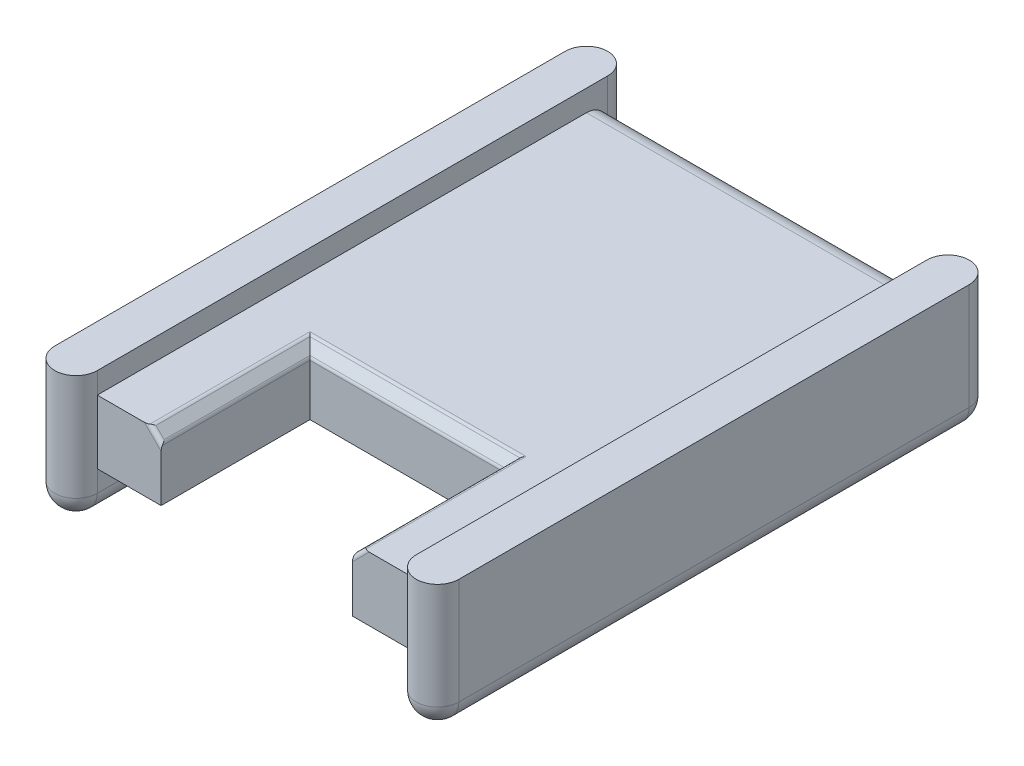
SolidWorks part; units mm, degrees
ref_plane "Front Plane" through (0, 0, 0) normal (0, 0, 1) x (1, 0, 0)
ref_plane "Top Plane" through (0, 0, 0) normal (0, 1, 0) x (1, 0, 0)
ref_plane "Right Plane" through (0, 0, 0) normal (1, 0, 0) x (0, 0, -1)
sketch "Sketch1" plane through (0, 0, 0) normal (0, 0, 1) x (1, 0, 0)
  line L1 (0, 0) -> (750, 0)
  line L2 (0, 0) -> (0, 150)
  line L3 (0, 150) -> (750, 150)
  line L4 (750, 0) -> (750, 150)
  dimension "D1" = 150
  dimension "D2" = 750
extrude "Boss-Extrude1" add sketch "Sketch1" against normal blind 1200
sketch "Sketch2" plane through (0, 150, 0) normal (0, 1, 0) x (1, 0, 0)
  line L0 (375, 1200) -> (375, 0) construction
  line L2 (0, 1200) -> (0, 0)
  line L4 (-100, 1200) -> (-100, 0)
  line L5 (750, 1200) -> (0, 1200) construction
  line L6 (750, 0) -> (0, 0) construction
  line L8 (850, 1200) -> (850, 0)
  line L10 (750, 1200) -> (750, 0)
  arc A4 (0, 1200) -> (-100, 1200) centre (-50, 1200) ccw
  arc A5 (850, 1200) -> (750, 1200) centre (800, 1200) ccw
  arc A6 (750, 0) -> (850, 0) centre (800, 0) ccw
  arc A7 (-100, 0) -> (0, 0) centre (-50, 0) ccw
  dimension "D1" = 100
extrude "Boss-Extrude8" add sketch "Sketch2" against normal blind 250 and the other way blind 50
fillet "Fillet2" radius 50 8 edges at (850, -100, -600) (800, -100, -1250) (750, -100, -600) (800, -100, 50) (-100, -100, -600) (-50, -100, 50) (0, -100, -600) (-50, -100, -1250)
fillet "Fillet3" radius 50 2 edges at (375, 150, -1200) (375, 0, -1200)
sketch "Sketch6" plane through (0, 150, 0) normal (0, 1, 0) x (1, 0, 0)
  line L0 (750, 0) -> (0, 0) construction
  line L5 (150, 0) -> (150, 350)
  line L6 (375, 0) -> (375, 423.0484) construction
  line L7 (600, 0) -> (150, 0)
  line L8 (600, 0) -> (600, 350)
  line L9 (600, 350) -> (150, 350)
  point P0 (375, 0)
  dimension "D3" = 350
extrude "Cut-Extrude1" cut sketch "Sketch6" against normal blind 250
chamfer "Chamfer1" distance 25 angle 45 1 edges at (375, 150, -350)
chamfer "Chamfer2" distance 25 angle 45 2 edges at (150, 150, -187.5) (600, 150, -187.5)
fillet "Fillet4" radius 10 8 edges at (137.5, 137.5, 0) (612.5, 137.5, 0) (600, 125, -175) (625, 150, -187.5) (375, 125, -350) (375, 150, -375) (125, 150, -187.5) (150, 125, -175)
